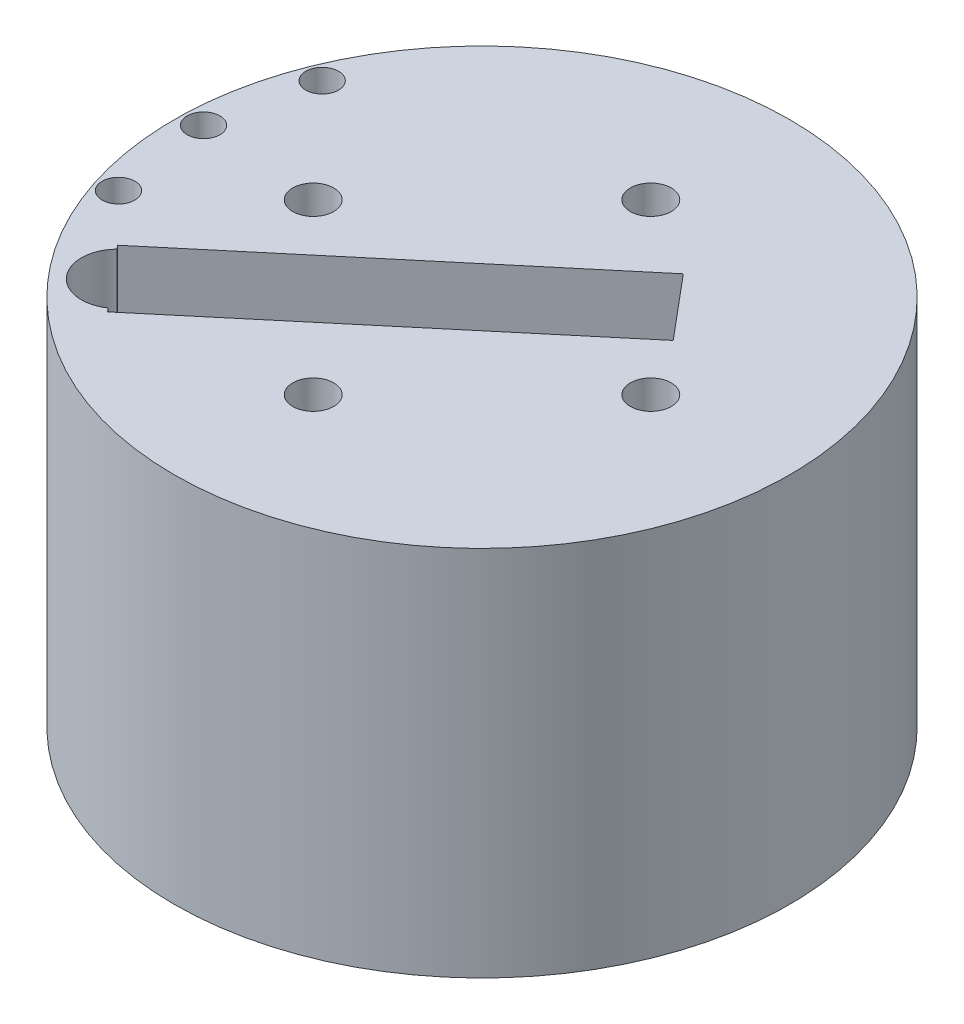
SolidWorks part; units mm, degrees
ref_plane "Front Plane" through (0, 0, 0) normal (0, 0, 1) x (1, 0, 0)
ref_plane "Top Plane" through (0, 0, 0) normal (0, 1, 0) x (1, 0, 0)
ref_plane "Right Plane" through (0, 0, 0) normal (1, 0, 0) x (0, 0, -1)
sketch "Sketch2" plane through (0, 0, 0) normal (0, 1, 0) x (1, 0, 0)
  circle A0 centre (0, 0) radius 47.6885
  dimension "D1" = 95.377
extrude "Boss-Extrude1" add sketch "Sketch2" along normal blind 57.658
sketch "Sketch4" plane through (0, 57.658, 0) normal (0, 1, 0) x (1, 0, 0)
  circle A1 centre (-26.162, 0) radius 3.175
  circle A2 centre (26.162, 0) radius 3.175
  circle A3 centre (0, 26.162) radius 3.175
  circle A4 centre (0, -26.162) radius 3.175
sketch "Sketch5" plane through (0, 57.658, 0) normal (0, 1, 0) x (1, 0, 0)
  line L0 (0, 0) -> (-44.6487, 1.4926)
  line L1 (0, 0) -> (-41.4455, 16.6734)
  line L2 (0, 0) -> (-42.4665, -13.8681)
  line L4 (0, 0) -> (-30.6943, -25.7555)
  circle A1 centre (-41.4455, 16.6734) radius 2.54
  circle A2 centre (0, 0) radius 44.6736
  circle A3 centre (-44.6487, 1.4926) radius 2.54
  circle A4 centre (-42.4665, -13.8681) radius 2.54
  circle A9 centre (-30.6943, -25.7555) radius 5.6388
  dimension "D3" = 11.2776
  dimension "D5" = 89.3472
  dimension "D1" = 20
  dimension "D2" = 20
  dimension "D6" = 21.915
  dimension "D4" = 40.0685
extrude "Cut-Extrude2" cut sketch "Sketch5" against normal through all contours A9 | A1 | A3 | A4
extrude "Cut-Extrude3" cut sketch "Sketch4" against normal through all
sketch "Sketch6" plane through (0, 57.658, 0) normal (0, 1, 0) x (1, 0, 0)
  line L1 (-27.0503, -30.9873) -> (20.6206, 9.0134)
  line L2 (-27.0503, -30.9873) -> (-35.2137, -21.2585)
  line L3 (-35.2137, -21.2585) -> (12.4572, 18.7422)
  line L4 (20.6206, 9.0134) -> (12.4572, 18.7422)
  dimension "D1" = 62.23
  dimension "D2" = 12.7
  dimension "D3" = 6.35
  dimension "D4" = 21.59
  dimension "D5" = 90
  dimension "D6" = 90
  dimension "D7" = 90
extrude "Cut-Extrude4" cut sketch "Sketch6" against normal blind 43.18
sketch "Sketch11" plane through (0, 0, 0) normal (0, -1, 0) x (1, 0, 0)
  circle A0 centre (0, 26.162) radius 6.35
  circle A1 centre (26.162, 0) radius 6.35
  circle A2 centre (0, -26.162) radius 6.35
  circle A3 centre (-26.162, 0) radius 6.35
  dimension "D1" = 12.7
  dimension "D2" = 12.7
  dimension "D3" = 12.7
  dimension "D4" = 12.7
extrude "Cut-Extrude7" cut sketch "Sketch11" against normal blind 7.62
sketch "Sketch14" plane through (0, 0, 0) normal (0, -1, 0) x (1, 0, 0)
  circle A0 centre (1.3569, -14.949) radius 2.067
  circle A1 centre (4.5237, 8.9723) radius 2.067
extrude "Cut-Extrude8" cut sketch "Sketch14" against normal blind 19.05
sketch "Sketch15" plane through (0, 0, 0) normal (0, -1, 0) x (1, 0, 0)
  line L0 (47.6885, 0) -> (-47.6885, 0)
  line L1 (0, -47.6885) -> (0, 47.6885)
  line L2 (-30.6943, 25.7555) -> (0, 0)
  circle A0 centre (0, 0) radius 47.6885 construction
  circle A1 centre (1.3569, -14.949) radius 2.067 construction
  circle A2 centre (1.3569, -14.949) radius 2.067 construction
  circle A3 centre (4.5237, 8.9723) radius 2.067 construction
  point P9 (0, 0)
  dimension "D1" = 1.3569
  dimension "D2" = 14.949
  dimension "D3" = 8.9723
  dimension "D4" = 4.5237
  dimension "D6" = 40
  dimension "D5" = 40.0685
equation "\"D4@Sketch5\"=(3.755/2)-(0.5/2)-0.05"
equation "\"D1@Sketch6\"=2.10 + (0.85-0.5)"
